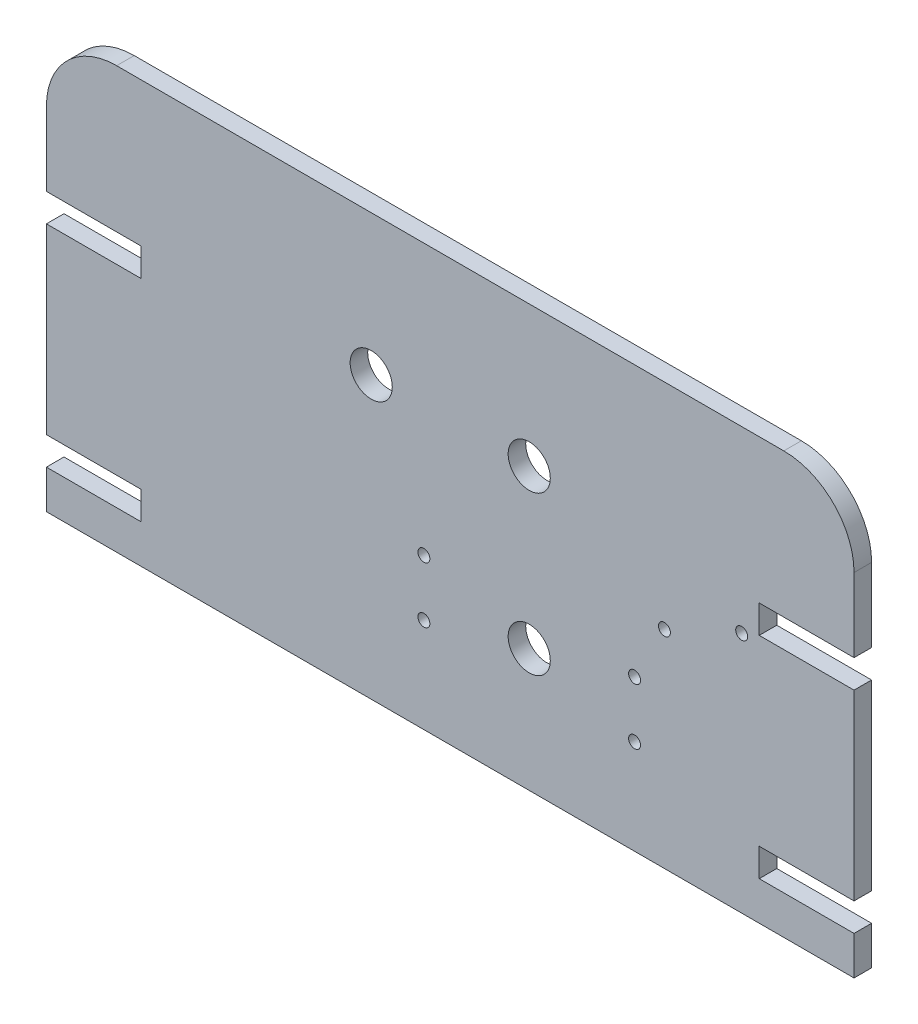
SolidWorks part; units mm, degrees
ref_plane "Front Plane" through (0, 0, 0) normal (0, 0, 1) x (1, 0, 0)
ref_plane "Top Plane" through (0, 0, 0) normal (0, 1, 0) x (1, 0, 0)
ref_plane "Right Plane" through (0, 0, 0) normal (1, 0, 0) x (0, 0, -1)
sketch "Sketch1" plane through (0, 0, 0) normal (0, 0, 1) x (1, 0, 0)
  line L1 (-115, -60) -> (115, -60)
  line L2 (-115, -60) -> (-115, 60)
  line L3 (-115, 60) -> (115, 60)
  line L4 (115, -60) -> (115, 60)
  line L5 (-115, -60) -> (115, 60) construction
  line L6 (-115, 60) -> (115, -60) construction
  point P0 (0, 0)
  dimension "D1" = 230
  dimension "D2" = 120
extrude "Boss-Extrude1" add sketch "Sketch1" along normal blind 5
sketch "Sketch2" plane through (0, 0, 0) normal (0, 0, -1) x (-1, 0, 0)
  line L0 (115, 11) -> (88, 11)
  line L1 (115, 60) -> (115, -60) construction
  line L2 (88, 11) -> (88, 19)
  line L3 (88, 19) -> (115, 19)
  line L4 (115, 19) -> (115, 11)
  line L5 (117.8, 19) -> (115.5, 19) construction
  line L6 (115.5, 11) -> (117.8, 11) construction
  line L7 (115, -49) -> (88, -49)
  line L8 (88, -41) -> (115, -41)
  line L9 (88, -49) -> (88, -41)
  line L10 (115, -41) -> (115, -49)
  line L11 (115.5, -49) -> (117.8, -49) construction
  line L12 (117.8, -41) -> (115.5, -41) construction
  line L13 (115, -40.5) -> (115, -30.5) construction
  line L14 (0, 2.75) -> (0, -2.75) construction
  line L15 (-115, -41) -> (-115, -49)
  line L16 (-88, -49) -> (-88, -41)
  line L17 (-88, -41) -> (-115, -41)
  line L18 (-115, -49) -> (-88, -49)
  line L19 (-115, 19) -> (-115, 11)
  line L20 (-88, 19) -> (-115, 19)
  line L21 (-88, 11) -> (-88, 19)
  line L22 (-115, 11) -> (-88, 11)
  dimension "D1" = 27
  dimension "D2" = 27
extrude "Cut-Extrude1" cut sketch "Sketch2" against normal up to next
sketch "Sketch3" plane through (0, 0, 5) normal (0, 0, 1) x (1, 0, 0)
  line L0 (-115, 20) -> (115, 20) construction
  line L1 (-115, 60) -> (-115, 19) construction
  line L2 (115, 19) -> (115, 60) construction
  line L3 (115, 60) -> (-115, 60) construction
  line L4 (22.5, 60) -> (22.5, -60) construction
  line L5 (-115, -60) -> (115, -60) construction
  circle A0 centre (22.5, 20) radius 6
  circle A1 centre (-22.5, 20) radius 6
  circle A2 centre (22.5, -25) radius 6
  dimension "D2" = 12
  dimension "D3" = 45
  dimension "D1" = 40
  dimension "D4" = 45
  dimension "D5" = 22.5
extrude "Cut-Extrude2" cut sketch "Sketch3" against normal up to next
sketch "Sketch5" plane through (0, 0, 5) normal (0, 0, 1) x (1, 0, 0)
  line L1 (-7.5, -33) -> (52.5, -33)
  line L2 (-7.5, -33) -> (-7.5, -17)
  line L3 (-7.5, -17) -> (52.5, -17)
  line L4 (52.5, -33) -> (52.5, -17)
  line L5 (-7.5, -33) -> (52.5, -17) construction
  line L6 (-7.5, -17) -> (52.5, -33) construction
  point P0 (22.5, -25)
  dimension "D1" = 16
  dimension "D2" = 60
hole_wizard "M3 Clearance Hole1" positions "3DSketch1" profile "Sketch6" hole size "M3" standard "ISO" end condition through all
sketch3d "3DSketch1"
  point P0 (-7.5, -17, 5)
  point P3 (52.5, -17, 5)
  point P6 (52.5, -33, 5)
  point P9 (-7.5, -33, 5)
sketch "Sketch6" plane through (-7.5, -17, 5) normal (1, 0, 0) x (0, -1, 0)
  line L0 (0, 0) -> (0, 5)
  line L1 (0, 5) -> (1.7, 5)
  line L2 (1.7, 5) -> (1.7, 0)
  line L5 (1.7, 0) -> (0, 0)
  line L11 (0, -6.35) -> (0, 107.95) construction
  dimension "Thru Hole Dia." = 3.4
  dimension "Thru Hole Depth" = 5
fillet "Fillet1" radius 20 2 edges at (115, 60, 2.5) (-115, 60, 2.5)
sketch "Sketch7" plane through (0, 0, 5) normal (0, 0, 1) x (1, 0, 0)
  line L0 (83, 9) -> (83, -1) construction
  line L1 (83, -1) -> (61, -1) construction
  line L2 (61, -1) -> (83, 9) construction
  line L3 (115, -41) -> (115, 11) construction
  line L4 (88, 11) -> (115, 11) construction
  circle A0 centre (61, -1) radius 1.7
  circle A1 centre (83, 9) radius 1.7
  point P1 (61, -1)
  point P3 (83, 9)
  dimension "D5" = 3.4
  dimension "D1" = 10
  dimension "D2" = 22
  dimension "D3" = 32
  dimension "D4" = 12
extrude "Cut-Extrude3" cut sketch "Sketch7" against normal up to next
